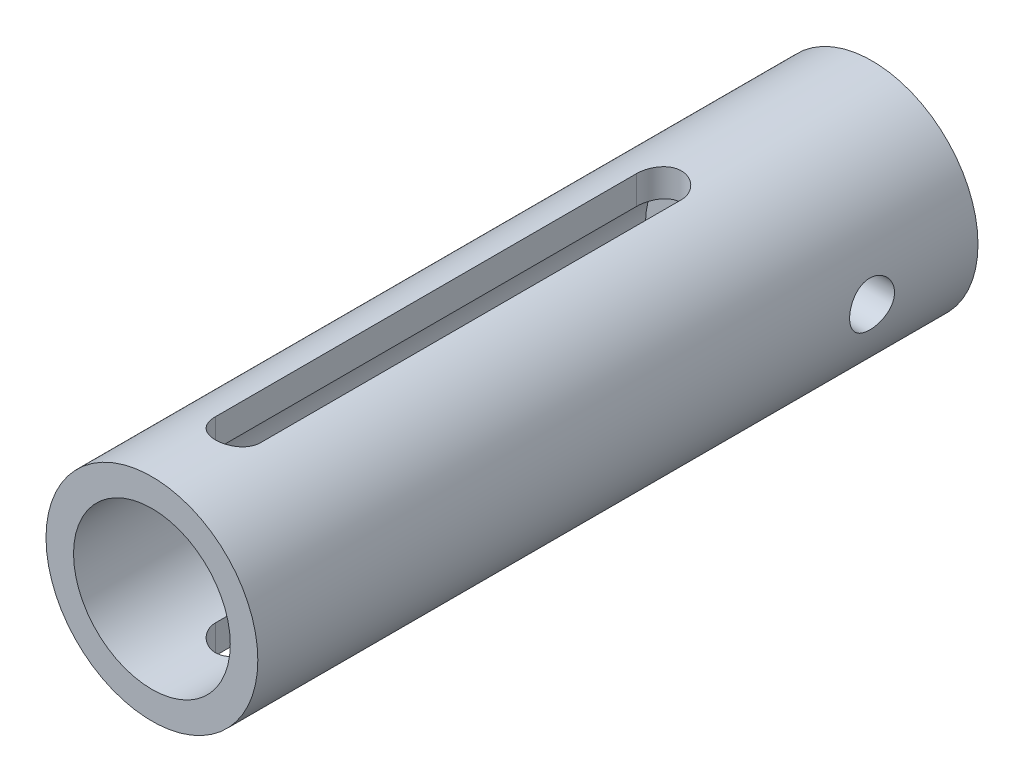
SolidWorks part; units mm, degrees
ref_plane "Front" through (0, 0, 0) normal (0, 0, 1) x (1, 0, 0)
ref_plane "Top" through (0, 0, 0) normal (0, 1, 0) x (1, 0, 0)
ref_plane "Right" through (0, 0, 0) normal (1, 0, 0) x (0, 0, -1)
sketch "Sketch1" plane through (0, 0, 0) normal (0, 0, 1) x (1, 0, 0)
  circle A0 centre (0, 0) radius 15.875
  circle A1 centre (0, 0) radius 11.7475
  dimension "D1" = 31.75
  dimension "D2" = 23.495
extrude "Boss-Extrude1" add sketch "Sketch1" along normal blind 101.6
hole_wizard "1/4 Clearance Slot1" positions "Sketch3" profile "Sketch2" size "1/4" standard "ANSI Inch" slot yes end condition through all
sketch "Sketch3" plane through (0, 0, 0) normal (0, 1, 0) x (1, 0, 0)
  line L0 (0, -92.075) -> (0, -22.225) construction
  line L1 (-15.875, -101.6) -> (15.875, -101.6) construction
  point P0 (0, -57.15)
  dimension "D1" = 9.525
sketch "Sketch2" plane through (0, 0, 57.15) normal (1, 0, 0) x (0, 0, -1)
  line L0 (0, 0) -> (0, 15.875)
  line L1 (0, 15.875) -> (3.3782, 15.875)
  line L2 (3.3782, 15.875) -> (3.3782, 0)
  line L5 (3.3782, 0) -> (0, 0)
  line L11 (0, -6.35) -> (0, 107.95) construction
  dimension "Thru Hole Dia." = 6.7564
  dimension "Thru Hole Depth" = 15.875
sketch "Sketch4" plane through (0, 0, 0) normal (0, 1, 0) x (1, 0, 0)
  line L0 (-3.3782, -88.6968) -> (-3.3782, -25.6032) construction
  line L1 (3.3782, -88.6968) -> (3.3782, -25.6032) construction
  line L2 (-3.3782, -88.6968) -> (-3.3782, -25.6032)
  line L3 (3.3782, -88.6968) -> (3.3782, -25.6032)
  arc A0 (3.3782, -25.6032) -> (-3.3782, -25.6032) centre (0, -25.6032) ccw construction
  arc A1 (-3.3782, -88.6968) -> (3.3782, -88.6968) centre (0, -88.6968) ccw construction
  arc A2 (3.3782, -25.6032) -> (-3.3782, -25.6032) centre (0, -25.6032) ccw
  arc A3 (-3.3782, -88.6968) -> (3.3782, -88.6968) centre (0, -88.6968) ccw
extrude "Cut-Extrude1" cut sketch "Sketch4" against normal up to next
sketch "Sketch7" plane through (0, 0, 0) normal (0, 0, -1) x (-1, 0, 0)
  circle A0 centre (0, 0) radius 15.875
extrude "Boss-Extrude2" add sketch "Sketch7" against normal blind 15.875
sketch "Sketch6" plane through (0, 0, 0) normal (1, 0, 0) x (0, 0, -1)
  circle A0 centre (-9.525, 0) radius 3.3655
extrude "Cut-Extrude3" cut sketch "Sketch6" against normal through all and the other way through all
sketch "Sketch8" plane through (0, 0, 0) normal (0, 0, -1) x (-1, 0, 0)
  circle A0 centre (0, 0) radius 15.875
extrude "Boss-Extrude3" add sketch "Sketch8" along normal blind 6.35
